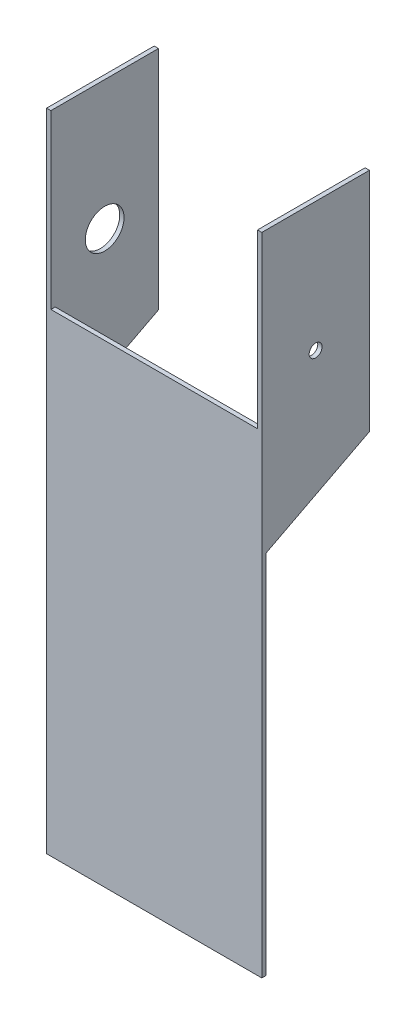
SolidWorks part; units mm, degrees
ref_plane "Alzado" through (0, 0, 0) normal (0, 0, 1) x (1, 0, 0)
ref_plane "Planta" through (0, 0, 0) normal (0, 1, 0) x (1, 0, 0)
ref_plane "Vista lateral" through (0, 0, 0) normal (1, 0, 0) x (0, 0, -1)
sketch "Croquis2" plane through (0, 0, 0) normal (0, 0, 1) x (1, 0, 0)
  line L1 (-32.8649, 52.5838) -> (17.1351, 52.5838)
  line L2 (-32.8649, 52.5838) -> (-32.8649, -97.4162)
  line L3 (-32.8649, -97.4162) -> (17.1351, -97.4162)
  line L4 (17.1351, 52.5838) -> (17.1351, -97.4162)
  dimension "D1" = 50
  dimension "D2" = 150
extrude "Saliente-Extruir1" add sketch "Croquis2" along normal blind 25
sketch "Croquis6" plane through (0, 0, 0) normal (0, 0, -1) x (-1, 0, 0)
  line L1 (-17.1351, 52.5838) -> (32.8649, 52.5838) construction
  line L2 (-16.1351, 52.5838) -> (-16.1351, 12.5838)
  line L4 (31.8649, 52.5838) -> (31.8649, 12.5838)
  line L5 (31.8649, 12.5838) -> (-16.1351, 12.5838)
  line L6 (-16.1351, 12.5838) -> (-16.1309, 12.4115)
  line L7 (-16.1351, 52.5838) -> (31.8649, 52.5838)
extrude "Cortar-Extruir1" cut sketch "Croquis6" against normal blind 25 contours L5 L4 L7 L2
shell "Vaciado2" thickness 1 removed face at (-7.8649, -97.4162, 12.5) removed face at (-7.8649, 12.5838, 12.5)
sketch "Croquis8" plane through (-32.8649, 0, 0) normal (-1, 0, 0) x (0, 0, 1)
  circle A0 centre (12.5, 22.5838) radius 4.5
extrude "Cortar-Extruir3" cut sketch "Croquis8" against normal blind 1
sketch "Croquis9" plane through (0, 0, 0) normal (0, 0, -1) x (-1, 0, 0)
  line L0 (-16.1351, 12.5838) -> (-16.1351, -97.4162)
  line L1 (32.8649, -97.4162) -> (-17.1351, -97.4162) construction
  line L2 (31.8649, 12.5838) -> (31.8649, -97.4162)
  line L3 (-16.1351, 12.5838) -> (31.8649, 12.5838)
  line L4 (-16.1351, -97.4162) -> (31.8649, -97.4162)
extrude "Cortar-Extruir4" cut sketch "Croquis9" against normal blind 10
sketch "Croquis10" plane through (-32.8649, 0, 0) normal (-1, 0, 0) x (0, 0, 1)
  line L0 (0, 0) -> (24, -12.4162)
  line L3 (24, -12.4162) -> (24, -97.4162)
  line L4 (25, -97.4162) -> (0, -97.4162) construction
  line L5 (24, -97.4162) -> (0, -97.4162)
  line L6 (0, -97.4162) -> (0, 0)
  dimension "D1" = 65
  dimension "D2" = 52.5838
extrude "Cortar-Extruir5" cut sketch "Croquis10" against normal blind 1
sketch "Croquis11" plane through (17.1351, 0, 0) normal (1, 0, 0) x (0, 0, -1)
  line L3 (-24, -12.4162) -> (-24, -97.4162)
  line L4 (-25, -97.4162) -> (0, -97.4162) construction
  line L5 (-24, -97.4162) -> (0, -97.4162)
  line L6 (0, -97.4162) -> (0, 0)
  line L7 (0, 0) -> (-24, -12.4162)
  circle A0 centre (-12.5, 22.5838) radius 1.5
  line M1 (0, -97.4162) -> (0, 52.5838)
  line M4 (-25, -97.4162) -> (0, -97.4162)
extrude "Cortar-Extruir6" cut sketch "Croquis11" against normal blind 1 contours L7 L3 M1 M4 region at (17.1351, -51.7417, 11.7277)
sketch "Croquis12" plane through (17.1351, 0, 0) normal (1, 0, 0) x (0, 0, -1)
  circle A0 centre (-12.5, 22.5838) radius 1.5
extrude "Cortar-Extruir7" cut sketch "Croquis12" against normal blind 1
